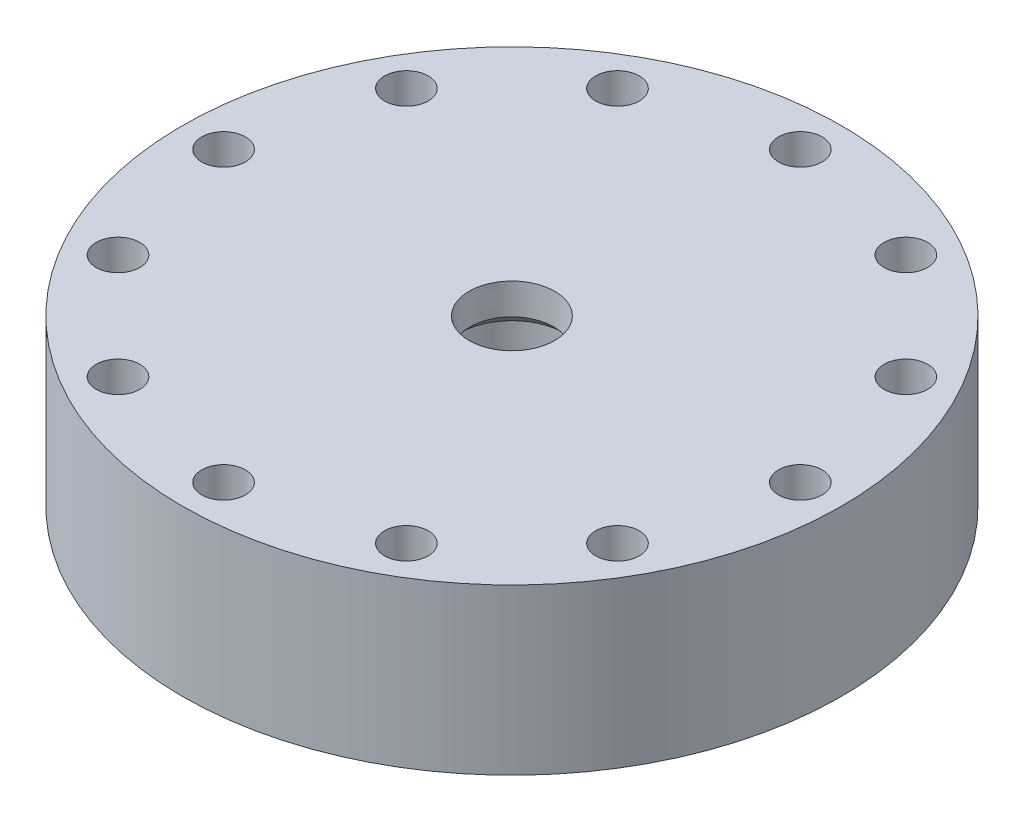
SolidWorks part; units mm, degrees
ref_plane "Front Plane" through (0, 0, 0) normal (0, 0, 1) x (1, 0, 0)
ref_plane "Top Plane" through (0, 0, 0) normal (0, 1, 0) x (1, 0, 0)
ref_plane "Right Plane" through (0, 0, 0) normal (1, 0, 0) x (0, 0, -1)
ref_axis "Axis1" through (0, 74.05, 0) along (0, -1, 0)
sketch "Sketch1" plane through (0, 0, 0) normal (0, 0, 1) x (1, 0, 0)
  line L2 (-76.2, 38.1) -> (0, 38.1)
  line L3 (0, 38.1) -> (0, 0)
  line L4 (0, 0) -> (-46.0375, 0)
  line L5 (-76.2, 38.1) -> (-76.2, 0)
  line L6 (-76.2, 0) -> (-52.3875, 0)
  line L9 (-52.3875, 9.525) -> (-46.0375, 15.875)
  line L10 (-46.0375, 0) -> (-46.0375, 15.875)
  line L11 (-52.3875, 0) -> (-52.3875, 9.525)
  dimension "D1" = 76.2
  dimension "D2" = 46.0375
  dimension "D3" = 45
  dimension "D4" = 6.35
  dimension "D5" = 9.525
  dimension "D8" = 38.1
revolve "Revolve1" add sketch "Sketch1" angle 360 about L3
ref_plane "Plane1" through (39.8696, 0, -23.0188) normal (0.866, 0, -0.5) x (0, 1, 0)
sketch "Sketch12" plane through (0, 0, 0) normal (0, 0, 1) x (1, 0, 0)
  line L13 (-0.7937, 23.8345) -> (-7.1437, 17.4845)
  line L20 (-7.1437, 17.4845) -> (-10.5066, 17.4845)
  line L26 (-7.1848, 33.5565) -> (-12.2456, 28.4957)
  line L27 (-12.2456, 28.4957) -> (-12.2456, 19.2235)
  line L28 (-12.2456, 19.2235) -> (-10.5066, 17.4845)
  line L29 (-0.7937, 23.8345) -> (-0.7937, 27.1655)
  line L30 (-0.7937, 27.1655) -> (-7.1848, 33.5565)
  line L31 (0, 0) -> (0, 38.1) construction
  line L32 (76.2, 38.1) -> (-76.2, 38.1) construction
  dimension "D1" = 135
  dimension "D2" = 0.7937
  dimension "D3" = 6.35
  dimension "D4" = 135
revolve "Cut-Revolve2" cut sketch "Sketch12" angle 360 about axis through (0, 74.05, 0) along (0, -1, 0)
sketch "Sketch26" plane through (0, 0, 0) normal (0, 0, 1) x (1, 0, 0)
  line L0 (0, 0) -> (0, 22.225)
  line L1 (0, 22.225) -> (-6.35, 15.875)
  line L2 (-6.35, 15.875) -> (-6.35, 9.525)
  line L3 (-6.35, 9.525) -> (-3.175, 6.35)
  line L4 (-3.175, 6.35) -> (-3.175, 0)
  line L5 (-46.0375, 0) -> (46.0375, 0) construction
  line L6 (-3.175, 0) -> (0, 0)
  line L7 (-4.191, 0) -> (-4.191, 5.9292)
  line L8 (-4.191, 5.9292) -> (-7.366, 9.1042)
  line L9 (-7.366, 9.1042) -> (-7.366, 12.4298)
  line L10 (-7.366, 12.4298) -> (-9.398, 14.4618)
  line L11 (-9.398, 14.4618) -> (-9.398, 9.6993)
  line L12 (-9.398, 9.6993) -> (-4.953, 5.2543)
  line L13 (-4.953, 5.2543) -> (-4.953, 0)
  line L14 (-4.953, 0) -> (-4.191, 0)
  dimension "D1" = 6.35
  dimension "D2" = 6.35
  dimension "D3" = 6.35
  dimension "D4" = 135
  dimension "D5" = 3.175
  dimension "D6" = 1.016
  dimension "D7" = 1.016
  dimension "D8" = 0.762
  dimension "D9" = 1.016
  dimension "D10" = 1.016
  dimension "D11" = 2.032
  dimension "D12" = 4.7625
revolve "Cut-Revolve3" cut sketch "Sketch26" angle 360 about axis through (0, 74.05, 0) along (0, -1, 0)
ref_axis "Axis2" through (-83.82, 0, 0) along (1, 0, 0)
hole_wizard "3/64 (0.04688) Diameter Hole2" positions "Sketch30" profile "Sketch31" hole size "3/64" standard "ANSI Inch"
sketch "Sketch30" plane through (0, 0, 0) normal (0, 0, 1) x (1, 0, 0)
  line L0 (6.35, 15.875) -> (-6.35, 15.875) construction
  point P0 (-8.7313, 11.9062)
  point P2 (-5.5563, 15.0813)
  dimension "D1" = 5.5562
  dimension "D2" = 3.175
  dimension "D3" = 3.175
  dimension "D4" = 0.7937
sketch "Sketch31" plane through (-8.7313, 11.9062, 0) normal (1, 0, 0) x (0, 1, 0)
  line L0 (0, 0) -> (0, 9.8827)
  line L1 (0, 9.8827) -> (0.5954, 9.525)
  line L2 (0.5954, 9.525) -> (0.5954, 0)
  line L5 (0.5954, 0) -> (0, 0)
  line L10 (0, 9.8827) -> (-0.5954, 9.525) construction
  line L11 (0, -6.35) -> (0, 107.95) construction
  dimension "Hole Dia." = 1.1908
  dimension "Hole Depth" = 9.525
  dimension "Drill Angle" = 118
pattern_circular "CirPattern6" count 3 over 360 about axis through (0, 74.05, 0) along (0, -1, 0) of "3/64 (0.04688) Diameter Hole2"
pattern_linear "LPattern1" count 2 spacing 25.4 along (1, 0, 0) of "Cut-Revolve3"
hole_wizard "3/64 (0.04688) Diameter Hole3" positions "Sketch34" profile "Sketch35" hole size "3/64" standard "ANSI Inch"
sketch "Sketch34" plane through (0, 0, 0) normal (0, 0, 1) x (1, 0, 0)
  line L0 (0, 0) -> (25.4, 0) construction
  line L1 (22.225, 0) -> (28.575, 0) construction
  line L3 (31.75, 15.875) -> (19.05, 15.875) construction
  point P0 (19.8438, 15.0813)
  point P2 (16.6687, 11.9062)
  dimension "D1" = 3.175
  dimension "D2" = 3.175
  dimension "D3" = 5.5562
  dimension "D4" = 0.7937
sketch "Sketch35" plane through (19.8438, 15.0813, 0) normal (1, 0, 0) x (0, 1, 0)
  line L0 (0, 0) -> (0, 9.8827)
  line L1 (0, 9.8827) -> (0.5954, 9.525)
  line L2 (0.5954, 9.525) -> (0.5954, 0)
  line L5 (0.5954, 0) -> (0, 0)
  line L10 (0, 9.8827) -> (-0.5954, 9.525) construction
  line L11 (0, -6.35) -> (0, 107.95) construction
  dimension "Hole Dia." = 1.1908
  dimension "Hole Depth" = 9.525
  dimension "Drill Angle" = 118
ref_axis "Axis3" through (25.4, 0, 0) along (0, 1, 0)
pattern_circular "CirPattern7" count 3 over 360 about axis through (25.4, 0, 0) along (0, 1, 0) of "3/64 (0.04688) Diameter Hole3"
ref_plane "Plane4" through (45.8623, 0, 4.0124) normal (0.9962, 0, 0.0872) x (0, 1, 0)
sketch "Sketch38" plane through (45.8623, 0, 4.0124) normal (0.9962, 0, 0.0872) x (0, 1, 0)
  line L0 (12.7963, 1.6838) -> (14.4801, 0)
  line L1 (14.4801, 0) -> (12.7963, -1.6838)
  line L2 (11.1125, 0) -> (14.4801, 0) construction
  arc A0 (12.7963, 1.6838) -> (12.7963, -1.6838) centre (11.1125, 0) ccw
  dimension "D2" = 2.3813
  dimension "D1" = 90
  dimension "D3" = 11.1125
extrude "Cut-Extrude3" cut sketch "Sketch38" against normal blind 9.525
pattern_circular "CirPattern8" count 6 over 360 about axis through (0, 74.05, 0) along (0, -1, 0) of "Cut-Extrude3"
sketch "Sketch27" plane through (39.8696, 0, -23.0188) normal (0.866, 0, -0.5) x (0, 1, 0)
  line L1 (9.6993, -2.3812) -> (11.9063, -2.3813)
  line L2 (11.9063, -2.3813) -> (14.2875, 0)
  line L3 (14.2875, 0) -> (11.9063, 2.3812)
  line L4 (11.9063, 2.3812) -> (9.6993, 2.3812)
  line L5 (11.9063, 2.3812) -> (11.9063, -2.3813) construction
  line L6 (9.6993, 9.398) -> (9.6993, -9.398) construction
  line L7 (10.4276, 0) -> (7.9375, 0) construction
  arc A0 (9.6993, 2.3812) -> (9.6993, -2.3812) centre (10.4276, 0) ccw
  dimension "D5" = 4.7625
  dimension "D1" = 135
  dimension "D2" = 135
  dimension "D3" = 7.9375
  dimension "D4" = 6.35
extrude "Cut-Extrude1" cut sketch "Sketch27" against normal blind 34.925
pattern_circular "CirPattern5" count 6 over 360 about axis through (0, 74.05, 0) along (0, -1, 0) of "LPattern1", "Cut-Extrude1", "CirPattern7"
sketch "Sketch36" plane through (0, 0, 0) normal (0, 0, 1) x (1, 0, 0)
  line L0 (-12.7, 13.3576) -> (-11.5775, 12.235)
  line L1 (-12.7, 13.3576) -> (-13.8225, 12.235)
  line L2 (-12.7, 11.1125) -> (-12.7, 13.3576) construction
  arc A0 (-11.5775, 12.235) -> (-13.8225, 12.235) centre (-12.7, 11.1125) cw
  dimension "D3" = 1.5875
  dimension "D1" = 90
  dimension "D2" = 12.7
  dimension "D4" = 11.1125
revolve "Cut-Revolve6" cut sketch "Sketch36" angle 360 about axis through (0, 74.05, 0) along (0, -1, 0)
hole_wizard "3/8 Clearance Hole1" positions "Sketch22" profile "Sketch23" hole size "3/8" standard "ANSI Inch" end condition through all
sketch "Sketch22" plane through (0, 38.1, 0) normal (0, 1, 0) x (1, 0, 0)
  line L0 (66.675, 0) -> (0, 0) construction
  point P0 (66.675, 0)
  dimension "D1" = 66.675
sketch "Sketch23" plane through (66.675, 38.1, 0) normal (1, 0, 0) x (0, 0, 1)
  line L0 (0, 0) -> (0, 38.1)
  line L1 (0, 38.1) -> (5.0419, 38.1)
  line L2 (5.0419, 38.1) -> (5.0419, 0)
  line L5 (5.0419, 0) -> (0, 0)
  line L11 (0, -6.35) -> (0, 107.95) construction
  dimension "Thru Hole Dia." = 10.0838
  dimension "Thru Hole Depth" = 38.1
pattern_circular "CirPattern4" count 12 over 360 about axis through (0, 74.05, 0) along (0, -1, 0) of "3/8 Clearance Hole1"
hole_wizard "1/2 NPT Tapped Hole2" positions "Sketch24" profile "Sketch25" size "1/2" standard "ANSI Inch"
sketch "Sketch24" plane through (0, 38.1, 0) normal (0, 1, 0) x (1, 0, 0)
  point P0 (0, 0)
cosmetic thread "Hole Thread2" parameters "D1"=13.462, "D2"=21.3288
sketch "Sketch25" plane through (0, 38.1, 0) normal (1, 0, 0) x (0, 0, 1)
  line L0 (0, 0) -> (0, 21.2395)
  line L1 (8.9281, 15.875) -> (0, 21.2395)
  line L2 (-8.9281, 15.875) -> (0, 21.2395) construction
  line L3 (8.9281, 15.875) -> (8.9281, 13.462)
  line L4 (8.9281, 13.462) -> (9.4797, 13.462)
  line L5 (9.4797, 13.462) -> (9.8828, 0)
  line L6 (-9.4797, 13.462) -> (-9.8828, 0) construction
  line L7 (9.8828, 0) -> (0, 0)
  line L8 (0, -6.35) -> (0, 107.95) construction
  line L11 (-8.9281, 13.462) -> (-9.4797, 13.462) construction
  dimension "Tap Drill Dia." = 17.8562
  dimension "Tap Drill Depth" = 15.875
  dimension "Thread Dia." = 19.7656
  dimension "Thread Angle" = 3.43
  dimension "Thread Depth" = 13.462
  dimension "Drill Angle" = 118
hole_wizard "1/2 NPT Tapped Hole1" positions "Sketch4" profile "Sketch5" size "1/2" standard "ANSI Inch"
sketch "Sketch4" plane through (0, 38.1, 0) normal (0, 1, 0) x (1, 0, 0)
  point P0 (0, 0)
sketch "Sketch5" plane through (0, 38.1, 0) normal (1, 0, 0) x (0, 0, 1)
  line L0 (0, 0) -> (0, 24.4145)
  line L1 (8.9281, 19.05) -> (0, 24.4145)
  line L2 (-8.9281, 19.05) -> (0, 24.4145) construction
  line L3 (8.9281, 19.05) -> (8.9281, 13.462)
  line L4 (8.9281, 13.462) -> (9.4797, 13.462)
  line L5 (9.4797, 13.462) -> (9.8828, 0)
  line L6 (-9.4797, 13.462) -> (-9.8828, 0) construction
  line L7 (9.8828, 0) -> (0, 0)
  line L8 (0, -6.35) -> (0, 107.95) construction
  line L11 (-8.9281, 13.462) -> (-9.4797, 13.462) construction
  dimension "Tap Drill Dia." = 17.8562
  dimension "Tap Drill Depth" = 19.05
  dimension "Thread Dia." = 19.7656
  dimension "Thread Angle" = 3.43
  dimension "Thread Depth" = 13.462
  dimension "Drill Angle" = 118
cosmetic thread "Hole Thread3" parameters "D1"=13.462, "D2"=18.8562
